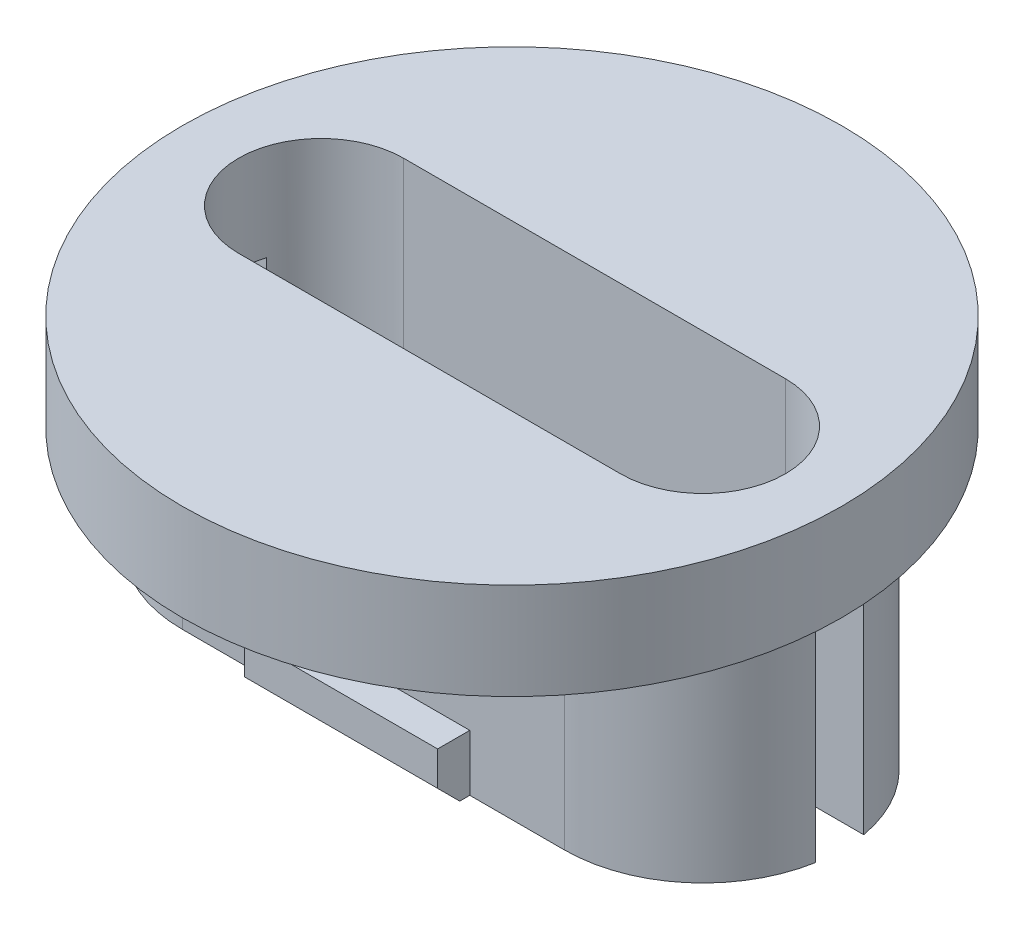
SolidWorks part; units mm, degrees
ref_plane "正面" through (0, 0, 0) normal (0, 0, 1) x (1, 0, 0)
ref_plane "平面" through (0, 0, 0) normal (0, 1, 0) x (1, 0, 0)
ref_plane "右側面" through (0, 0, 0) normal (1, 0, 0) x (0, 0, -1)
sketch "ｽｹｯﾁ1" plane through (0, 0, 0) normal (0, 1, 0) x (1, 0, 0)
  line L0 (-10.2, 0) -> (10.2, 0) construction
  line L1 (-5.6, 0) -> (3.9, 0) construction
  line L2 (-5.6, 3.55) -> (3.9, 3.55) construction
  line L3 (-5.6, -3.55) -> (3.9, -3.55) construction
  line L4 (-5.6, 3.45) -> (3.9, 3.45)
  line L5 (-5.6, -3.45) -> (3.9, -3.45)
  line L6 (-5.6, 2.05) -> (3.9, 2.05)
  line L7 (-5.6, -2.05) -> (3.9, -2.05)
  arc A0 (-5.6, 3.55) -> (-5.6, -3.55) centre (-5.6, 0) ccw construction
  arc A1 (3.9, -3.55) -> (3.9, 3.55) centre (3.9, 0) ccw construction
  arc A2 (3.9, -3.45) -> (3.9, 3.45) centre (3.9, 0) ccw
  arc A3 (-5.6, 3.45) -> (-5.6, -3.45) centre (-5.6, 0) ccw
  arc A4 (3.9, -2.05) -> (3.9, 2.05) centre (3.9, 0) ccw
  arc A5 (-5.6, 2.05) -> (-5.6, -2.05) centre (-5.6, 0) ccw
  point P4 (-0.85, 0)
  dimension "D1" = 7.1
  dimension "D2" = 9.5
  dimension "D3" = 0.1
  dimension "D4" = 1.5
extrude "ﾎﾞｽ - 押し出し1" add sketch "ｽｹｯﾁ1" along normal blind 4
sketch "ｽｹｯﾁ2" plane through (0, 4, 0) normal (0, 1, 0) x (1, 0, 0)
  line L0 (-0.85, 2.05) -> (-0.85, -2.05) construction
  line L6 (-5.6, -2.05) -> (3.9, -2.05)
  line L7 (3.9, 2.05) -> (-5.6, 2.05)
  line L8 (-5.6, -2.05) -> (3.9, -2.05)
  line L9 (3.9, 2.05) -> (-5.6, 2.05)
  circle A0 centre (-0.85, 0) radius 8.2
  arc A6 (3.9, -2.05) -> (3.9, 2.05) centre (3.9, 0) ccw
  arc A7 (-5.6, 2.05) -> (-5.6, -2.05) centre (-5.6, 0) ccw
  arc A8 (3.9, -2.05) -> (3.9, 2.05) centre (3.9, 0) ccw
  arc A9 (-5.6, 2.05) -> (-5.6, -2.05) centre (-5.6, 0) ccw
  dimension "D1" = 16.4
  dimension "D2" = 0
extrude "ﾎﾞｽ - 押し出し2" add sketch "ｽｹｯﾁ2" along normal blind 2.4
sketch "ｽｹｯﾁ3" plane through (0, 0, 0) normal (0, -1, 0) x (1, 0, 0)
  line L0 (-0.85, 2.05) -> (-0.85, 5.9261) construction
  line L1 (-5.6, 2.05) -> (3.9, 2.05) construction
  line L2 (-3.85, 3.45) -> (-3.85, 2.05)
  line L3 (-5.6, 3.45) -> (3.9, 3.45) construction
  line L4 (-3.85, 3.45) -> (2.15, 3.45)
  line L5 (-3.85, 2.05) -> (2.15, 2.05)
  line L6 (2.15, 3.45) -> (2.15, 2.05)
  line L7 (-5.6, 0) -> (-10.7278, 0) construction
  line L8 (-3.85, -2.05) -> (2.15, -2.05)
  line L9 (-3.85, -3.45) -> (2.15, -3.45)
  line L10 (-3.85, -3.45) -> (-3.85, -2.05)
  line L11 (2.15, -2.05) -> (2.15, -3.45)
  dimension "D1" = 3
extrude "ﾎﾞｽ - 押し出し3" add sketch "ｽｹｯﾁ3" along normal blind 1
sketch "ｽｹｯﾁ4" plane through (0, -1, 0) normal (0, -1, 0) x (1, 0, 0)
  line L0 (2.15, 2.05) -> (2.15, 3.45) construction
  line L1 (-3.85, 3.45) -> (-3.85, 2.05) construction
  line L2 (-0.85, 0) -> (-4.1643, 0) construction
  line L3 (2.15, 3.45) -> (-3.85, 3.45) construction
  line L4 (-0.85, 1.75) -> (-0.85, -1.75) construction
  line L6 (1.55, -3.15) -> (-3.25, -3.15)
  line L7 (1.55, -3.15) -> (1.55, -4.25)
  line L8 (1.55, -4.25) -> (-3.25, -4.25)
  line L9 (-3.25, -3.15) -> (-3.25, -4.25)
  line L10 (-3.25, 3.15) -> (-3.25, 4.25)
  line L11 (1.55, 4.25) -> (-3.25, 4.25)
  line L12 (1.55, 3.15) -> (1.55, 4.25)
  line L13 (1.55, 3.15) -> (-3.25, 3.15)
  dimension "D1" = 0.6
  dimension "D2" = 0.6
  dimension "D3" = 0.8
extrude "ﾎﾞｽ - 押し出し4" add sketch "ｽｹｯﾁ4" against normal blind 1.4
sketch "ｽｹｯﾁ5" plane through (0, 0, -3.45) normal (0, 0, -1) x (-1, 0, 0)
  line L0 (-2.15, 0) -> (-2.15, 4)
  line L1 (-3.9, 4) -> (5.6, 4) construction
  line L2 (3.85, 0) -> (3.85, 4)
  line L3 (-2.15, 4) -> (-2.35, 4)
  line L4 (-2.35, 0) -> (-2.35, 4)
  line L5 (-2.35, 0) -> (-2.15, 0)
  line L6 (4.05, 0) -> (4.05, 4)
  line L7 (-2.15, 4) -> (3.85, 4) construction
  line L8 (-2.35, 4.2) -> (4.05, 4.2) construction
  line L9 (3.85, 0) -> (4.05, 0)
  line L10 (3.85, 4) -> (4.05, 4)
  line L12 (4.05, 0) -> (4.05, 4.2) construction
  line L13 (-2.35, 0) -> (-2.35, 4.2) construction
  dimension "D1" = 0.2
sketch "ｽｹｯﾁ6" plane through (0, 0, 0) normal (0, -1, 0) x (1, 0, 0)
  line L0 (-3.85, -3.45) -> (-3.85, -2.05) construction
  line L1 (-3.85, -2.05) -> (-5.6, -2.05) construction
  line L2 (-5.6, 2.05) -> (-3.85, 2.05) construction
  line L3 (-3.85, 2.05) -> (-3.85, 3.45) construction
  line L4 (-3.85, 3.45) -> (-5.6, 3.45) construction
  line L5 (-5.6, -3.45) -> (-3.85, -3.45) construction
  line L6 (2.15, -2.05) -> (2.15, -3.45) construction
  line L7 (2.15, -3.45) -> (3.9, -3.45) construction
  line L8 (3.9, 3.45) -> (2.15, 3.45) construction
  line L9 (2.15, 3.45) -> (2.15, 2.05) construction
  line L10 (2.15, 2.05) -> (3.9, 2.05) construction
  line L11 (3.9, -2.05) -> (2.15, -2.05) construction
  line L12 (-3.85, -3.45) -> (-3.85, -2.05)
  line L13 (-3.85, -2.05) -> (-5.6, -2.05)
  line L14 (-5.6, 2.05) -> (-3.85, 2.05)
  line L15 (-3.85, 2.05) -> (-3.85, 3.45)
  line L16 (-3.85, 3.45) -> (-5.6, 3.45)
  line L17 (-5.6, -3.45) -> (-3.85, -3.45)
  line L18 (2.15, -2.05) -> (2.15, -3.45)
  line L19 (2.15, -3.45) -> (3.9, -3.45)
  line L20 (3.9, 3.45) -> (2.15, 3.45)
  line L21 (2.15, 3.45) -> (2.15, 2.05)
  line L22 (2.15, 2.05) -> (3.9, 2.05)
  line L23 (3.9, -2.05) -> (2.15, -2.05)
  arc A0 (-5.6, 2.05) -> (-5.6, -2.05) centre (-5.6, 0) ccw construction
  arc A1 (-5.6, 3.45) -> (-5.6, -3.45) centre (-5.6, 0) ccw construction
  arc A2 (3.9, -3.45) -> (3.9, 3.45) centre (3.9, 0) ccw construction
  arc A3 (3.9, -2.05) -> (3.9, 2.05) centre (3.9, 0) ccw construction
  arc A4 (-5.6, 2.05) -> (-5.6, -2.05) centre (-5.6, 0) ccw
  arc A5 (-5.6, 3.45) -> (-5.6, -3.45) centre (-5.6, 0) ccw
  arc A6 (3.9, -3.45) -> (3.9, 3.45) centre (3.9, 0) ccw
  arc A7 (3.9, -2.05) -> (3.9, 2.05) centre (3.9, 0) ccw
extrude "ﾎﾞｽ - 押し出し5" add sketch "ｽｹｯﾁ6" along normal up to vertex (1 mm away) up to point (-3.25, -1, 3.45)
chamfer "面取り1" distance 0.55 angle 45 1 edges at (-0.85, -1, 4.25)
chamfer "面取り2" distance 0.55 angle 45 1 edges at (-0.85, -1, -4.25)
sketch "ｽｹｯﾁ7" plane through (0, 0, 0) normal (1, 0, 0) x (0, 0, -1)
  line L0 (0, 4) -> (0, -1) construction
  line L1 (-3.45, -1) -> (3.45, -1) construction
  line L2 (-3.45, 4) -> (0, 4) construction
  line L3 (-0.6, 4) -> (0.6, 4)
  line L4 (-0.6, 4) -> (-0.6, -1)
  line L5 (-0.6, -1) -> (0.6, -1)
  line L6 (0.6, 4) -> (0.6, -1)
  dimension "D1" = 0.6
  dimension "D2" = 0.6
extrude "ｶｯﾄ - 押し出し1" cut sketch "ｽｹｯﾁ7" against normal mid plane 20
